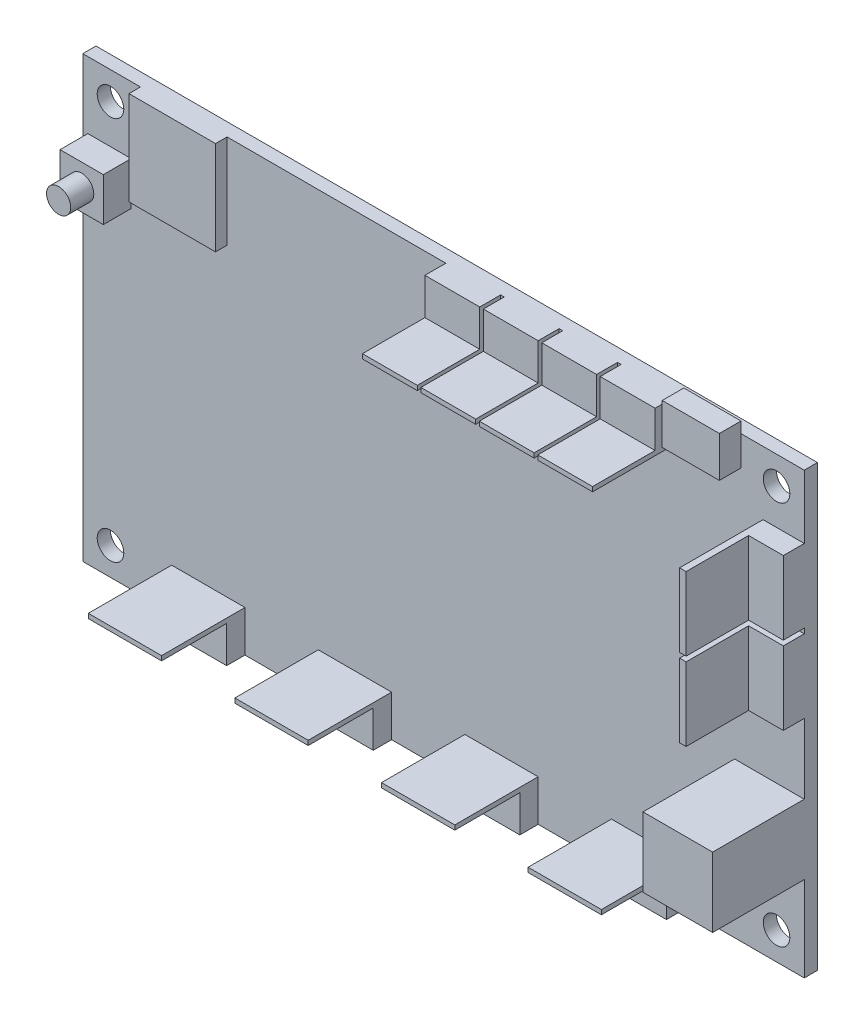
SolidWorks part; units mm, degrees
ref_plane "Front Plane" through (0, 0, 0) normal (0, 0, 1) x (1, 0, 0)
ref_plane "Top Plane" through (0, 0, 0) normal (0, 1, 0) x (1, 0, 0)
ref_plane "Right Plane" through (0, 0, 0) normal (1, 0, 0) x (0, 0, -1)
sketch "Sketch1" plane through (0, 0, 0) normal (0, 0, 1) x (1, 0, 0)
  line L1 (0, 0) -> (100, 0)
  line L2 (0, 0) -> (0, 60.96)
  line L3 (0, 60.96) -> (100, 60.96)
  line L4 (100, 0) -> (100, 60.96)
  dimension "D1" = 60.96
  dimension "D2" = 100
extrude "Boss-Extrude1" add sketch "Sketch1" along normal blind 1.8288
sketch "Sketch2" plane through (0, 0, 1.8288) normal (0, 0, 1) x (1, 0, 0)
  line L0 (0, 0) -> (100, 0) construction
  line L1 (12.319, 5.715) -> (22.479, 5.715)
  line L2 (12.319, 5.715) -> (12.319, 0)
  line L3 (12.319, 0) -> (22.479, 0)
  line L4 (22.479, 5.715) -> (22.479, 0)
  line L5 (12.319, 5.715) -> (22.479, 0) construction
  line L6 (12.319, 0) -> (22.479, 5.715) construction
  line L7 (0, 60.96) -> (0, 0) construction
  line L8 (32.639, 5.715) -> (42.799, 0) construction
  line L9 (32.639, 0) -> (42.799, 5.715) construction
  line L10 (32.639, 5.715) -> (42.799, 5.715)
  line L11 (42.799, 5.715) -> (42.799, 0)
  line L12 (32.639, 0) -> (42.799, 0)
  line L13 (32.639, 5.715) -> (32.639, 0)
  line L14 (52.959, 5.715) -> (63.119, 0) construction
  line L15 (52.959, 0) -> (63.119, 5.715) construction
  line L16 (52.959, 5.715) -> (63.119, 5.715)
  line L17 (63.119, 5.715) -> (63.119, 0)
  line L18 (52.959, 0) -> (63.119, 0)
  line L19 (52.959, 5.715) -> (52.959, 0)
  line L20 (73.279, 5.715) -> (83.439, 0) construction
  line L21 (73.279, 0) -> (83.439, 5.715) construction
  line L22 (73.279, 5.715) -> (83.439, 5.715)
  line L23 (83.439, 5.715) -> (83.439, 0)
  line L24 (73.279, 0) -> (83.439, 0)
  line L25 (73.279, 5.715) -> (73.279, 0)
  line L26 (12.319, 5.715) -> (32.639, 5.715) construction
  line L27 (100, 0) -> (100, 60.96) construction
  line L28 (100, 52.16) -> (94.285, 52.16)
  line L29 (100, 52.16) -> (100, 42)
  line L30 (100, 42) -> (94.285, 42)
  line L31 (94.285, 52.16) -> (94.285, 42)
  line L32 (100, 52.16) -> (94.285, 42) construction
  line L33 (100, 42) -> (94.285, 52.16) construction
  line L34 (100, 60.96) -> (0, 60.96) construction
  line L35 (100, 41.32) -> (94.285, 41.32)
  line L36 (100, 41.32) -> (100, 31.16)
  line L37 (100, 31.16) -> (94.285, 31.16)
  line L38 (94.285, 41.32) -> (94.285, 31.16)
  line L39 (100, 41.32) -> (94.285, 31.16) construction
  line L40 (100, 31.16) -> (94.285, 41.32) construction
  point P4 (17.399, 2.8575)
  point P27 (97.1425, 47.08)
  point P34 (97.1425, 36.24)
  dimension "D1" = 10.16
  dimension "D2" = 5.715
  dimension "D3" = 12.319
  dimension "D5" = 20.32
  dimension "D6" = 21
  dimension "D7" = 8.8
  dimension "D4" = 4
extrude "4 pin molex" add sketch "Sketch2" along normal blind 11.557
sketch "Sketch3" plane through (83.439, 0, 0) normal (1, 0, 0) x (0, 0, -1)
  line L0 (-13.3858, 5.715) -> (-1.8288, 5.715) construction
  line L1 (-13.3858, 0) -> (-4.3688, 0)
  line L2 (-13.3858, 0) -> (-13.3858, 5.08)
  line L3 (-13.3858, 5.08) -> (-4.3688, 5.08)
  line L4 (-4.3688, 0) -> (-4.3688, 5.08)
  line L5 (-13.3858, 0) -> (-4.3688, 5.08) construction
  line L6 (-13.3858, 5.08) -> (-4.3688, 0) construction
  line L7 (-1.8288, 0) -> (-1.8288, 31.16) construction
  point P4 (-8.8773, 2.54)
  dimension "D1" = 0.635
  dimension "D2" = 2.54
extrude "Cut-Extrude1" cut sketch "Sketch3" against normal through all
sketch "Sketch7" plane through (0, 31.16, 0) normal (0, -1, 0) x (-1, 0, 0)
  line L1 (-100, -13.3858) -> (-95.185, -13.3858)
  line L2 (-100, -13.3858) -> (-100, -4.7288)
  line L3 (-100, -4.7288) -> (-95.185, -4.7288)
  line L4 (-95.185, -13.3858) -> (-95.185, -4.7288)
  line L5 (-100, -13.3858) -> (-95.185, -4.7288) construction
  line L6 (-100, -4.7288) -> (-95.185, -13.3858) construction
  line L8 (-94.285, -13.3858) -> (-94.285, -1.8288) construction
  line L9 (-83.439, -1.8288) -> (-100, -1.8288) construction
  point P4 (-97.5925, -9.0573)
  dimension "D1" = 0.9
  dimension "D2" = 2.9
extrude "Cut-Extrude2" cut sketch "Sketch7" against normal blind 24.6
sketch "Sketch4" plane through (0, 0, 1.8288) normal (0, 0, 1) x (1, 0, 0)
  line L0 (100, 0) -> (100, 31.16) construction
  line L1 (100, 21.463) -> (90.348, 21.463)
  line L2 (100, 21.463) -> (100, 11.811)
  line L3 (100, 11.811) -> (90.348, 11.811)
  line L4 (90.348, 21.463) -> (90.348, 11.811)
  line L5 (100, 21.463) -> (90.348, 11.811) construction
  line L6 (100, 11.811) -> (90.348, 21.463) construction
  line L7 (83.439, 0) -> (100, 0) construction
  point P4 (95.174, 16.637)
  dimension "D1" = 9.652
  dimension "D2" = 9.652
  dimension "D3" = 11.811
extrude "Power Connector" add sketch "Sketch4" along normal blind 12.7
sketch "Sketch5" plane through (0, 0, 1.8288) normal (0, 0, 1) x (1, 0, 0)
  line L0 (100, 21.463) -> (100, 31.16) construction
  line L1 (83.3122, 56.8452) -> (91.237, 56.8452)
  line L2 (83.3122, 56.8452) -> (83.3122, 62.484)
  line L3 (83.3122, 62.484) -> (91.237, 62.484)
  line L4 (91.237, 56.8452) -> (91.237, 62.484)
  line L5 (83.3122, 56.8452) -> (91.237, 62.484) construction
  line L6 (83.3122, 62.484) -> (91.237, 56.8452) construction
  line L7 (100, 60.96) -> (0, 60.96) construction
  point P4 (87.2746, 59.6646)
  dimension "D1" = 7.9248
  dimension "D2" = 5.6388
  dimension "D3" = 8.763
  dimension "D4" = 1.524
extrude "MicroUSB" add sketch "Sketch5" along normal blind 3
sketch "Sketch6" plane through (0, 0, 1.8288) normal (0, 0, 1) x (1, 0, 0)
  line L0 (83.3122, 60.96) -> (0, 60.96) construction
  line L1 (8, 60.96) -> (20, 60.96)
  line L2 (8, 60.96) -> (8, 47.96)
  line L3 (8, 47.96) -> (20, 47.96)
  line L4 (20, 60.96) -> (20, 47.96)
  line L5 (8, 60.96) -> (20, 47.96) construction
  line L6 (8, 47.96) -> (20, 60.96) construction
  line L7 (0, 60.96) -> (0, 0) construction
  point P4 (14, 54.46)
  dimension "D1" = 12
  dimension "D2" = 13
  dimension "D3" = 8
extrude "MicroSD" add sketch "Sketch6" along normal blind 1.6
sketch "Sketch8" plane through (0, 0, 1.8288) normal (0, 0, 1) x (1, 0, 0)
  line L0 (0, 60.96) -> (0, 0) construction
  line L1 (0.7, 51.71) -> (6.7, 51.71)
  line L2 (0.7, 51.71) -> (0.7, 45.71)
  line L3 (0.7, 45.71) -> (6.7, 45.71)
  line L4 (6.7, 51.71) -> (6.7, 45.71)
  line L5 (0.7, 51.71) -> (6.7, 45.71) construction
  line L6 (0.7, 45.71) -> (6.7, 51.71) construction
  line L7 (8, 60.96) -> (0, 60.96) construction
  point P4 (3.7, 48.71)
  dimension "D1" = 6
  dimension "D2" = 6
  dimension "D3" = 6.7
  dimension "D4" = 9.25
extrude "Boss-Extrude6" add sketch "Sketch8" along normal blind 3.85
sketch "Sketch9" plane through (0, 0, 5.6788) normal (0, 0, 1) x (1, 0, 0)
  line L0 (0.7, 48.71) -> (3.7, 48.71) construction
  line L1 (0.7, 51.71) -> (0.7, 45.71) construction
  line L2 (3.7, 48.71) -> (3.7, 51.71) construction
  line L3 (6.7, 51.71) -> (0.7, 51.71) construction
  circle A0 centre (3.7, 48.71) radius 1.675
  dimension "D1" = 3.35
extrude "Boss-Extrude7" add sketch "Sketch9" along normal blind 3.2
sketch "Sketch10" plane through (0, 0, 1.8288) normal (0, 0, 1) x (1, 0, 0)
  line L0 (83.3122, 60.96) -> (20, 60.96) construction
  line L1 (82.22, 60.96) -> (74.62, 60.96)
  line L2 (82.22, 60.96) -> (82.22, 55.245)
  line L3 (82.22, 55.245) -> (74.62, 55.245)
  line L4 (74.62, 60.96) -> (74.62, 55.245)
  line L5 (82.22, 60.96) -> (74.62, 55.245) construction
  line L6 (82.22, 55.245) -> (74.62, 60.96) construction
  line L7 (100, 52.16) -> (100, 60.96) construction
  line L8 (74.12, 55.245) -> (66.52, 55.245)
  line L9 (66.52, 60.96) -> (66.52, 55.245)
  line L10 (74.12, 55.245) -> (66.52, 60.96) construction
  line L11 (74.12, 60.96) -> (66.52, 55.245) construction
  line L12 (74.12, 60.96) -> (66.52, 60.96)
  line L13 (74.12, 60.96) -> (74.12, 55.245)
  line L14 (66.02, 55.245) -> (58.42, 55.245)
  line L15 (58.42, 60.96) -> (58.42, 55.245)
  line L16 (66.02, 55.245) -> (58.42, 60.96) construction
  line L17 (66.02, 60.96) -> (58.42, 55.245) construction
  line L18 (66.02, 60.96) -> (58.42, 60.96)
  line L19 (66.02, 60.96) -> (66.02, 55.245)
  line L20 (57.92, 55.245) -> (50.32, 55.245)
  line L21 (50.32, 60.96) -> (50.32, 55.245)
  line L22 (57.92, 55.245) -> (50.32, 60.96) construction
  line L23 (57.92, 60.96) -> (50.32, 55.245) construction
  line L24 (57.92, 60.96) -> (50.32, 60.96)
  line L25 (57.92, 60.96) -> (57.92, 55.245)
  line L26 (82.22, 55.245) -> (74.12, 55.245) construction
  point P4 (78.42, 58.1025)
  dimension "D1" = 7.6
  dimension "D2" = 5.715
  dimension "D3" = 17.78
  dimension "D5" = 8.1
  dimension "D4" = 4
extrude "Boss-Extrude8" add sketch "Sketch10" along normal blind 11.557
sketch "Sketch11" plane through (82.22, 0, 0) normal (1, 0, 0) x (0, 0, -1)
  line L0 (-13.3858, 55.245) -> (-1.8288, 55.245) construction
  line L1 (-13.3858, 60.96) -> (-4.7288, 60.96)
  line L2 (-13.3858, 60.96) -> (-13.3858, 55.88)
  line L3 (-13.3858, 55.88) -> (-4.7288, 55.88)
  line L4 (-4.7288, 60.96) -> (-4.7288, 55.88)
  line L5 (-13.3858, 60.96) -> (-4.7288, 55.88) construction
  line L6 (-13.3858, 55.88) -> (-4.7288, 60.96) construction
  line L7 (-1.8288, 52.16) -> (-1.8288, 60.96) construction
  point P4 (-9.0573, 58.42)
  dimension "D1" = 0.635
  dimension "D2" = 2.9
extrude "Cut-Extrude3" cut sketch "Sketch11" against normal blind 36.449
sketch "Sketch13" plane through (0, 0, 1.8288) normal (0, 0, 1) x (1, 0, 0)
  line L0 (8, 60.96) -> (0, 60.96) construction
  line L1 (0, 60.96) -> (0, 0) construction
  line L2 (100, 0) -> (100, 11.811) construction
  line L3 (83.439, 0) -> (100, 0) construction
  circle A0 centre (3.8415, 57.1185) radius 1.8415
  circle A1 centre (3.8415, 3.8415) radius 1.8415
  circle A2 centre (96.1585, 3.8415) radius 1.8415
  circle A3 centre (96.1585, 57.1185) radius 1.8415
  dimension "D1" = 3.683
  dimension "D2" = 2
  dimension "D3" = 2
  dimension "D4" = 2
  dimension "D5" = 2
extrude "Cut-Extrude4" cut sketch "Sketch13" against normal blind 36.449
